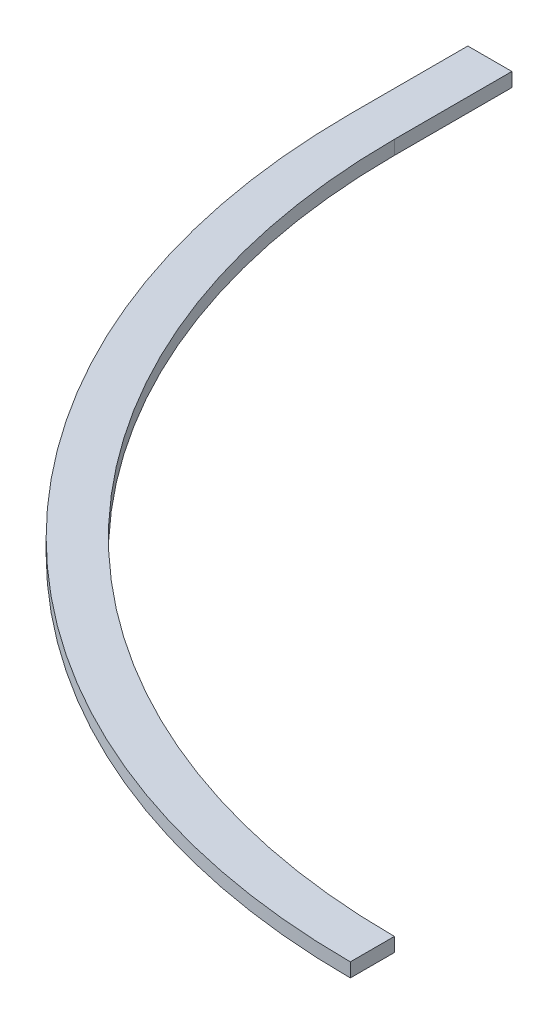
SolidWorks part; units mm, degrees
material "Pine"
ref_plane "Front Plane" through (0, 0, 0) normal (0, 0, 1) x (1, 0, 0)
ref_plane "Top Plane" through (0, 0, 0) normal (0, 1, 0) x (1, 0, 0)
ref_plane "Right Plane" through (0, 0, 0) normal (1, 0, 0) x (0, 0, -1)
sketch "Sketch2" plane through (0, 0, 0) normal (0, 1, 0) x (1, 0, 0)
  line L0 (0, 0) -> (-500, 0)
  line L1 (0, 0) -> (0, -500)
  circle A0 centre (0, 0) radius 500
  circle A1 centre (0, 0) radius 470
  dimension "D1" = 1000
  dimension "D2" = 30
extrude "Boss-Extrude1" add sketch "Sketch2" along normal blind 9.525 contours A1 L0 A0 L1 region at (-337.3402, 0, 337.3402)
sketch "Sketch3" plane through (0, 0, 0) normal (0, 0, -1) x (-1, 0, 0)
  line L8 (470, 0) -> (500, 0)
  line L9 (500, 0) -> (500, 9.525)
  line L10 (500, 9.525) -> (470, 9.525)
  line L11 (470, 9.525) -> (470, 0)
  line L12 (470, 0) -> (500, 0)
  line L13 (500, 0) -> (500, 9.525)
  line L14 (500, 9.525) -> (470, 9.525)
  line L15 (470, 9.525) -> (470, 0)
  dimension "D1" = 0
extrude "Boss-Extrude2" add sketch "Sketch3" along normal blind 80
sketch "Sketch4" plane through (0, 9.525, 0) normal (0, 1, 0) x (1, 0, 0)
  line L1 (-500, 80) -> (0, 80) construction
  line L2 (-500, 80) -> (-500, -500) construction
  line L3 (-500, -500) -> (0, -500) construction
  line L4 (0, 80) -> (0, -500) construction
